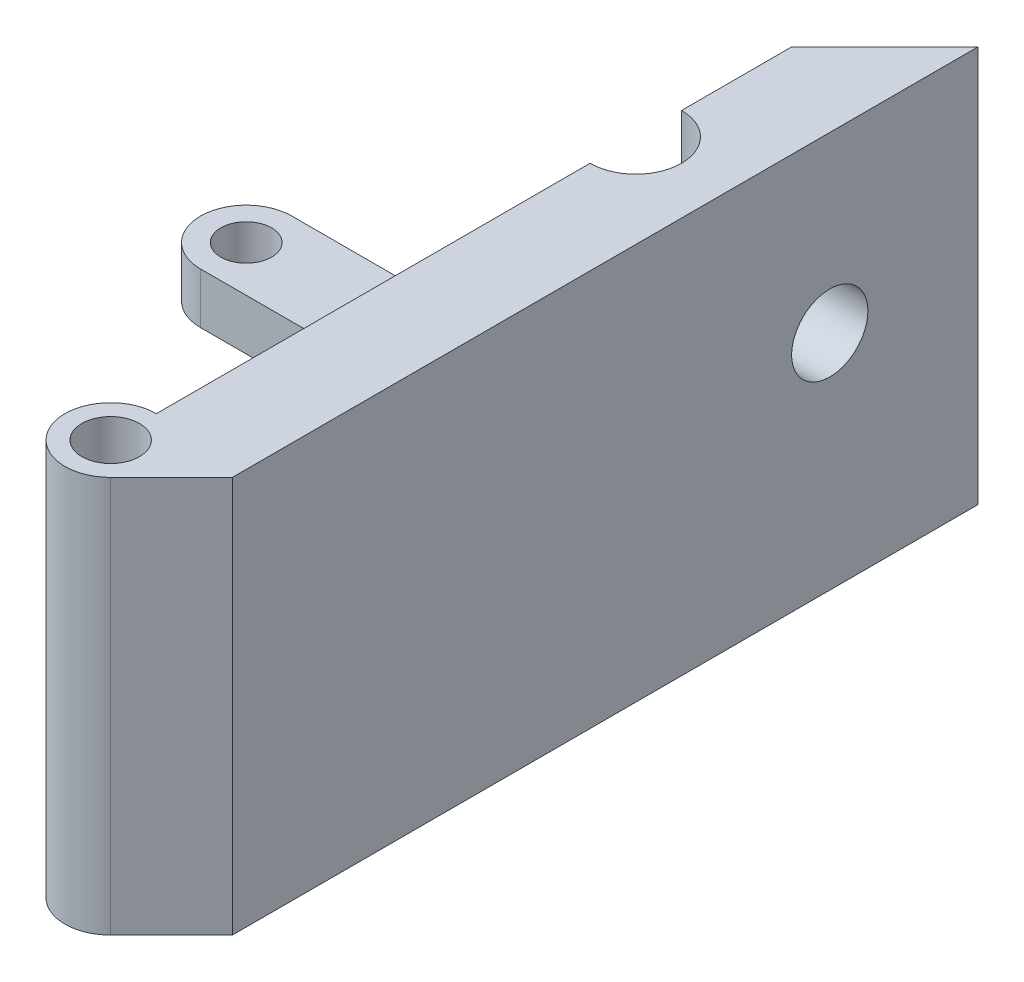
SolidWorks part; units mm, degrees
material "6061-T6 (SS)"
ref_plane "Front Plane" through (0, 0, 0) normal (0, 0, 1) x (1, 0, 0)
ref_plane "Top Plane" through (0, 0, 0) normal (0, 1, 0) x (1, 0, 0)
ref_plane "Right Plane" through (0, 0, 0) normal (1, 0, 0) x (0, 0, -1)
ref_axis "Axis1" through (0, 0, 55) along (0, 0, -1)
sketch "outline" plane through (0, 0, 0) normal (0, 1, 0) x (1, 0, 0)
  line L1 (-25, -100) -> (125, -100)
  line L2 (-25, -100) -> (-25, 100)
  line L3 (-25, 100) -> (125, 100)
  line L4 (125, -100) -> (125, 100)
  line L5 (-25, -100) -> (125, 100) construction
  line L6 (-25, 100) -> (125, -100) construction
  line L7 (125, 100) -> (275, 100)
  line L8 (125, 100) -> (125, -100)
  line L9 (125, -100) -> (275, -100)
  line L10 (275, 100) -> (275, -100)
  line L11 (125, 100) -> (275, -100) construction
  line L12 (125, -100) -> (275, 100) construction
  point P4 (50, 0)
  point P11 (200, 0)
  dimension "D1" = 150
  dimension "D2" = 200
  dimension "D3" = 150
  dimension "D4" = 50
sketch "x_carriage_plate" plane through (0, 0, 0) normal (0, 1, 0) x (1, 0, 0)
  line L0 (20, -4.5) -> (20, 0) construction
  line L1 (0, 0) -> (64, 0) construction
  line L2 (0, 0) -> (0, 37.5) construction
  line L3 (10, 47.5) -> (54, 47.5) construction
  line L4 (64, 0) -> (64, 37.5) construction
  line L5 (0, 0) -> (64, 47.5) construction
  line L6 (0, 47.5) -> (64, 0) construction
  line L7 (44, -4.5) -> (44, 0) construction
  circle A0 centre (13, 14.25) radius 1.5
  circle A1 centre (30.5, 30.15) radius 1.5
  circle A2 centre (12, 35.6) radius 2.5
  circle A3 centre (52, 35.6) radius 2.5
  arc A4 (64, 37.5) -> (54, 47.5) centre (54, 37.5) ccw construction
  arc A5 (10, 47.5) -> (0, 37.5) centre (10, 37.5) ccw construction
  circle A6 centre (55.5, 23.05) radius 1.5
  circle A7 centre (41.5, 23.05) radius 1.5
  arc A8 (20, -4.5) -> (44, -4.5) centre (32, -4.5) ccw construction
  circle A9 centre (32, -4.6) radius 3.6
  point P4 (32, 23.75)
  dimension "D7" = 5
  dimension "D11" = 3
  dimension "D12" = 10
  dimension "D16" = 24
  dimension "D19" = 7.2
  dimension "D1" = 64
  dimension "D2" = 47.5
  dimension "D3" = 13
  dimension "D4" = 12
  dimension "D5" = 30.5
  dimension "D6" = 40
  dimension "D8" = 11.9
  dimension "D9" = 14.25
  dimension "D10" = 30.15
  dimension "D13" = 8.5
  dimension "D14" = 22.5
  dimension "D15" = 24.45
  dimension "D17" = 4.5
  dimension "D18" = 32
  dimension "D20" = 4.6
sketch "front_profile" plane through (0, 0, 0) normal (0, 1, 0) x (1, 0, 0)
  line L0 (0, 0) -> (64, 0) construction
  line L1 (37.35, 43.55) -> (59.65, 43.55)
  line L2 (37.35, 43.55) -> (37.35, -18.75)
  line L3 (37.35, -18.75) -> (59.65, -18.75)
  line L4 (59.65, 43.55) -> (59.65, -18.75)
  line L5 (37.35, 43.55) -> (59.65, -18.75) construction
  line L6 (37.35, -18.75) -> (59.65, 43.55) construction
  line L7 (48.5, 12.4) -> (48.5, 23.05) construction
  line L8 (48.5, 23.05) -> (41.5, 23.05) construction
  line L9 (48.5, 23.05) -> (55.5, 23.05) construction
  line L10 (48.5, 12.4) -> (23.5, 12.4) construction
  line L15 (64, 0) -> (64, 37.5) construction
  line L16 (69.5, -6.2877) -> (69.5, -3.1123)
  line L21 (69.5, -3.1123) -> (66.75, -1.5246)
  line L22 (66.75, -1.5246) -> (64, -3.1123)
  line L23 (43.5, 44.75) -> (53.5, 44.75)
  line L24 (43.5, 44.75) -> (43.5, 43.55)
  line L25 (43.5, 43.55) -> (53.5, 43.55)
  line L26 (53.5, 44.75) -> (53.5, 43.55)
  line L27 (43.5, 44.75) -> (53.5, 43.55) construction
  line L28 (43.5, 43.55) -> (53.5, 44.75) construction
  line L30 (23.5, 90.5) -> (65.5, 90.5)
  line L31 (23.5, 90.5) -> (23.5, 48.5)
  line L32 (23.5, 48.5) -> (65.5, 48.5)
  line L33 (65.5, 90.5) -> (65.5, 48.5)
  line L34 (23.5, 90.5) -> (65.5, 48.5) construction
  line L35 (23.5, 48.5) -> (65.5, 90.5) construction
  line L36 (10, 47.5) -> (54, 47.5) construction
  line L37 (29, 85) -> (60, 85) construction
  line L38 (29, 85) -> (29, 54) construction
  line L39 (29, 54) -> (60, 54) construction
  line L40 (60, 85) -> (60, 54) construction
  line L41 (29, 85) -> (60, 54) construction
  line L42 (29, 54) -> (60, 85) construction
  line L43 (64, -3.1123) -> (64, -6.2877)
  line L44 (64, -6.2877) -> (66.75, -7.8754)
  line L45 (66.75, -7.8754) -> (69.5, -6.2877)
  circle A0 centre (29, 54) radius 1.5
  circle A1 centre (60, 54) radius 1.5
  circle A2 centre (60, 85) radius 1.5
  circle A3 centre (29, 85) radius 1.5
  circle A4 centre (44.5, 69.5) radius 2.5
  circle A6 centre (66.75, -4.7) radius 2.75 construction
  circle A7 centre (66.75, -4.7) radius 1.7 construction
  circle A8 centre (66.75, -4.7) radius 4.7
  circle A9 centre (52.5, 69.5) radius 2.5
  arc A10 (52.5, 69.5) -> (77.2192, 54) centre (60, 54) cw construction
  circle A14 centre (60, 54) radius 1.7 construction
  circle A15 centre (60, 54) radius 3.2 construction
  arc A16 (48.8726, 0) -> (62.8779, -7.3641) centre (48.8726, -17) cw
  arc A17 (69.8364, -1.1554) -> (64, 11.6654) centre (81, 11.6654) cw
  point P0 (48.5, 12.4)
  point P15 (48.5, 44.15)
  point P30 (44.5, 69.5)
  point P37 (44.5, 69.5)
  dimension "D12" = 3
  dimension "D13" = 5
  dimension "D4" = 5.5
  dimension "D5" = 3.4
  dimension "D16" = 3.4
  dimension "D18" = 17
  dimension "D1" = 62.3
  dimension "D2" = 22.3
  dimension "D3" = 18.75
  dimension "D8" = 1.2
  dimension "D9" = 10
  dimension "D10" = 42
  dimension "D11" = 31
  dimension "D7" = 4
  dimension "D14" = 8
  dimension "D15" = 25
  dimension "D19" = 1
  dimension "D6" = 3
  dimension "D17" = 1.5
sketch "idler_door" plane through (0, 0, 0) normal (0, 1, 0) x (1, 0, 0)
  line L0 (60, 85) -> (60, 54) construction
  line L1 (65.5, 90.5) -> (65.5, 48.5) construction
  line L2 (23.5, 48.5) -> (65.5, 90.5) construction
  line L3 (60, 87.7) -> (60, 88.7) construction
  line L4 (60, 56.7) -> (60, 82.3) construction
  line L5 (61.9092, 52.0908) -> (65.5, 55.6816) construction
  line L6 (65.5, 99.7) -> (65.5, 55.6816) construction
  line L7 (52.5, 66.8) -> (60, 66.8) construction
  line L8 (52.5, 72.2) -> (60, 72.2) construction
  line L9 (50.5, 93.2) -> (80.5, 93.2)
  line L10 (50.5, 93.2) -> (50.5, 88.7)
  line L11 (50.5, 88.7) -> (80.5, 88.7)
  line L12 (80.5, 93.2) -> (80.5, 88.7)
  line L13 (50.5, 93.2) -> (80.5, 88.7) construction
  line L14 (50.5, 88.7) -> (80.5, 93.2) construction
  line L15 (80.5, 94.45) -> (84.5, 94.45)
  line L16 (80.5, 94.45) -> (80.5, 87.45)
  line L17 (80.5, 87.45) -> (84.5, 87.45)
  line L18 (84.5, 94.45) -> (84.5, 87.45)
  line L19 (80.5, 94.45) -> (84.5, 87.45) construction
  line L20 (80.5, 87.45) -> (84.5, 94.45) construction
  line L21 (60, 94.2) -> (65.5, 99.7) construction
  line L22 (60, 88.7) -> (60, 93.2) construction
  line L23 (60, 93.2) -> (60, 94.2) construction
  line L25 (53, 94.45) -> (56, 94.45)
  line L26 (53, 94.45) -> (53, 87.45)
  line L27 (53, 87.45) -> (56, 87.45)
  line L28 (56, 94.45) -> (56, 87.45)
  line L29 (53, 94.45) -> (56, 87.45) construction
  line L30 (53, 87.45) -> (56, 94.45) construction
  circle A2 centre (52.5, 69.5) radius 1.5
  circle A5 centre (52.5, 69.5) radius 2.7
  circle A8 centre (60, 85) radius 1.7 construction
  circle A9 centre (60, 85) radius 2.7 construction
  circle A11 centre (60, 54) radius 1.7 construction
  circle A12 centre (60, 54) radius 1.7
  circle A14 centre (60, 54) radius 2.7
  point P8 (65.5, 90.95)
  point P36 (82.5, 90.95)
  point P43 (54.5, 90.95)
  dimension "D1" = 1
  dimension "D4" = 4.5
  dimension "D5" = 3
  dimension "D8" = 5.5
  dimension "D9" = 4
  dimension "D11" = 3.4
  dimension "D16" = 4
  dimension "D3" = 15
  dimension "D7" = 7
  dimension "D2" = 45
  dimension "D10" = 30
  dimension "D13" = 1
  dimension "D14" = 3
  dimension "D15" = 7
  dimension "D6" = 1.2
  dimension "D12" = 1
sketch "side_profile" plane through (0, 0, 0) normal (0, 1, 0) x (1, 0, 0)
  line L0 (125, 100) -> (275, 100) construction
  line L1 (255, 100) -> (275, 100)
  line L2 (255, 100) -> (255, -100)
  line L3 (255, -100) -> (275, -100)
  line L4 (275, 100) -> (275, -100)
  line L5 (255, 100) -> (275, -100) construction
  line L6 (255, -100) -> (275, 100) construction
  line L7 (201.8, 100) -> (201.8, -100) construction
  line L8 (228.15, -10) -> (248.15, -10)
  line L9 (228.15, -10) -> (228.15, -30)
  line L10 (228.15, -30) -> (248.15, -30)
  line L11 (248.15, -10) -> (248.15, -30)
  line L12 (228.15, -10) -> (248.15, -30) construction
  line L13 (228.15, -30) -> (248.15, -10) construction
  line L14 (221.8, 12) -> (224.3, 12)
  line L15 (221.8, 12) -> (221.8, -35.5)
  line L16 (221.8, -35.5) -> (224.3, -35.5)
  line L17 (224.3, 12) -> (224.3, -35.5)
  line L18 (221.8, 12) -> (224.3, -35.5) construction
  line L19 (221.8, -35.5) -> (224.3, 12) construction
  line L20 (209.7, 55) -> (249.7, 55)
  line L21 (209.7, 55) -> (209.7, 13)
  line L22 (209.7, 13) -> (249.7, 13)
  line L23 (249.7, 55) -> (249.7, 13)
  line L24 (209.7, 55) -> (249.7, 13) construction
  line L25 (209.7, 13) -> (249.7, 55) construction
  line L26 (185.7, 36.5) -> (209.7, 36.5)
  line L27 (185.7, 36.5) -> (185.7, 31.5)
  line L28 (185.7, 31.5) -> (209.7, 31.5)
  line L29 (209.7, 36.5) -> (209.7, 31.5)
  line L30 (185.7, 36.5) -> (209.7, 31.5) construction
  line L31 (185.7, 31.5) -> (209.7, 36.5) construction
  line L32 (207.7, 23) -> (209.7, 23)
  line L33 (207.7, 23) -> (207.7, 45)
  line L34 (207.7, 45) -> (209.7, 45)
  line L35 (209.7, 23) -> (209.7, 45)
  line L36 (207.7, 23) -> (209.7, 45) construction
  line L37 (207.7, 45) -> (209.7, 23) construction
  line L38 (125, -100) -> (275, -100) construction
  line L39 (186.3, -35.5) -> (186.3, 55)
  line L40 (187.7, 34.9851) -> (207.7, 34.9851) construction
  line L41 (221.8, -35.5) -> (224.3, -35.5)
  line L42 (221.8, -35.5) -> (221.8, -52)
  line L43 (221.8, -52) -> (224.3, -52)
  line L44 (224.3, -35.5) -> (224.3, -52)
  line L45 (221.8, -35.5) -> (224.3, -52) construction
  line L46 (221.8, -52) -> (224.3, -35.5) construction
  line L47 (190.7, 34) -> (204.7, 34) construction
  line L48 (197.7, 34) -> (197.7, 34.9851) construction
  line L49 (249.7, 34) -> (209.7, 34) construction
  line L50 (199.8, 28) -> (203.8, 28)
  line L51 (199.8, 28) -> (199.8, -35.0215)
  line L52 (199.8, -35.0215) -> (203.8, -35.0215)
  line L53 (203.8, 28) -> (203.8, -35.0215)
  line L54 (199.8, 28) -> (203.8, -35.0215) construction
  line L55 (199.8, -35.0215) -> (203.8, 28) construction
  line L56 (214.7, 18.5) -> (186.3, 18.5) construction
  line L57 (214.7, 49.5) -> (214.7, 18.5) construction
  line L58 (186.3, 20.2) -> (214.7, 20.2)
  line L59 (186.3, 20.2) -> (186.3, 16.8)
  line L60 (186.3, 16.8) -> (214.7, 16.8)
  line L61 (214.7, 20.2) -> (214.7, 16.8)
  line L62 (186.3, 20.2) -> (214.7, 16.8) construction
  line L63 (186.3, 16.8) -> (214.7, 20.2) construction
  line L64 (186.3, 55) -> (183.3, 55)
  line L69 (183.3, 55) -> (183.3, -35.5)
  line L70 (183.3, -35.5) -> (186.3, -35.5)
  line L71 (186.3, 49.5) -> (214.7, 49.5) construction
  line L72 (190.7, 38.5) -> (204.7, 38.5)
  line L73 (190.7, 38.5) -> (190.7, 29.5)
  line L74 (190.7, 29.5) -> (204.7, 29.5)
  line L75 (204.7, 38.5) -> (204.7, 29.5)
  line L76 (190.7, 38.5) -> (204.7, 29.5) construction
  line L77 (190.7, 29.5) -> (204.7, 38.5) construction
  line L78 (186.3, 51.2) -> (214.7, 51.2)
  line L79 (186.3, 51.2) -> (186.3, 47.8)
  line L80 (186.3, 47.8) -> (214.7, 47.8)
  line L81 (214.7, 51.2) -> (214.7, 47.8)
  line L82 (186.3, 51.2) -> (214.7, 47.8) construction
  line L83 (186.3, 47.8) -> (214.7, 51.2) construction
  line L84 (185.3, 52.2) -> (215.7, 52.2) construction
  line L85 (215.7, 52.2) -> (215.7, 46.8) construction
  line L86 (185.3, 46.8) -> (215.7, 46.8) construction
  line L87 (185.3, 52.2) -> (185.3, 46.8) construction
  circle A3 centre (196.55, 55.45) radius 2.25
  circle A4 centre (196.55, 55.45) radius 3.25 construction
  point P4 (265, 0)
  point P8 (238.15, -20)
  point P13 (197.7, 34)
  point P16 (223.05, -11.75)
  point P22 (229.7, 34)
  point P35 (208.7, 34)
  point P39 (223.05, -43.75)
  point P42 (201.8, -3.5107)
  point P49 (197.7, 34.9851)
  point P54 (200.5, 49.5)
  point P68 (214.7, 34)
  point P75 (0, 0)
  dimension "D13" = 5
  dimension "D10" = 42
  dimension "D25" = 4.5
  dimension "D1" = 20
  dimension "D2" = 20
  dimension "D3" = 6.85
  dimension "D4" = 20
  dimension "D5" = 2.5
  dimension "D6" = 3.85
  dimension "D7" = 47.5
  dimension "D8" = 22
  dimension "D9" = 40
  dimension "D11" = 24
  dimension "D12" = 5.3
  dimension "D14" = 2
  dimension "D15" = 22
  dimension "D16" = 5.9
  dimension "D17" = 20
  dimension "D18" = 12.1
  dimension "D19" = 16.5
  dimension "D20" = 35.5
  dimension "D21" = 20
  dimension "D22" = 14
  dimension "D23" = 2.9
  dimension "D26" = 23.4
  dimension "D27" = 15.5
  dimension "D28" = 4
  dimension "D32" = 3.4
  dimension "D31" = 5
  dimension "D33" = 31
  dimension "D34" = 6
  dimension "D35" = 3
  dimension "D24" = 9
  dimension "D36" = 1
  dimension "D29" = 1
  dimension "D30" = 1
sketch "Sketch1" plane through (0, 0, 0) normal (0, 1, 0) x (1, 0, 0)
  line L0 (60, 94.2) -> (65.5, 99.7) construction
  line L1 (60, 93.2) -> (60, 94.2) construction
  line L2 (60, 88.7) -> (60, 93.2) construction
  line L3 (60, 87.7) -> (60, 88.7) construction
  line L4 (65.5, 99.7) -> (65.5, 55.6816) construction
  line L5 (60, 56.7) -> (60, 82.3) construction
  line L6 (61.9092, 52.0908) -> (65.5, 55.6816) construction
  line L7 (60, 94.2) -> (65.5, 99.7)
  line L8 (60, 93.2) -> (60, 94.2)
  line L9 (60, 88.7) -> (60, 93.2)
  line L10 (60, 87.7) -> (60, 88.7)
  line L11 (65.5, 99.7) -> (65.5, 55.6816)
  line L12 (60, 56.7) -> (60, 82.3)
  line L13 (61.9092, 52.0908) -> (65.5, 55.6816)
  circle A0 centre (60, 54) radius 1.7 construction
  circle A1 centre (60, 54) radius 2.7 construction
  circle A2 centre (60, 54) radius 1.7
  arc A3 (60, 56.7) -> (61.9092, 52.0908) centre (60, 54) ccw
  circle A4 centre (60, 85) radius 2.7 construction
  arc A5 (60, 82.3) -> (60, 87.7) centre (60, 85) ccw
  arc A6 (60, 87.7) -> (60, 82.3) centre (60, 85) ccw construction
  arc A7 (61.9092, 52.0908) -> (60, 56.7) centre (60, 54) ccw construction
extrude "Boss-Extrude1" add sketch "Sketch1" along normal mid plane 23.4
sketch "Sketch2" plane through (65.5, 0, 0) normal (1, 0, 0) x (0, 0, -1)
  line L0 (55.6816, 11.7) -> (99.7, 11.7) construction
  circle A0 centre (90.95, 1.45) radius 2.25
  point P4 (0, 0)
  point P7 (0, 0)
  point P10 (0, 0)
  dimension "D2" = 4.5
  dimension "D1" = 10.25
extrude "Cut-Extrude1" cut sketch "Sketch2" against normal through all
sketch "Sketch3" plane through (0, -11.7, 0) normal (0, -1, 0) x (1, 0, 0)
  line L0 (52.5, -66.8) -> (60, -66.8) construction
  line L1 (52.5, -72.2) -> (60, -72.2) construction
  line L2 (52.5, -66.8) -> (60, -66.8)
  line L3 (52.5, -72.2) -> (60, -72.2)
  line L4 (60, -66.8) -> (60, -72.2)
  circle A0 centre (52.5, -69.5) radius 1.5 construction
  circle A1 centre (52.5, -69.5) radius 2.7 construction
  circle A2 centre (52.5, -69.5) radius 1.5
  arc A3 (52.5, -66.8) -> (52.5, -72.2) centre (52.5, -69.5) ccw
  arc A4 (52.5, -72.2) -> (52.5, -66.8) centre (52.5, -69.5) ccw construction
extrude "Boss-Extrude2" add sketch "Sketch3" against normal blind 3 from offset 2 offset against normal yes
extrude "Boss-Extrude3" add sketch "Sketch3<2>" against normal blind 3 from offset 19 offset against normal yes
sketch "Sketch3<2>" plane through (0, -11.7, 0) normal (0, -1, 0) x (1, 0, 0) same geometry as "Sketch3"
equation "\"D1@front_profile\" = 62.300mm"
equation "\"D19@side_profile\" = 4.5 + 12"
equation "\"D16@side_profile\"=2.900mm + 3"
